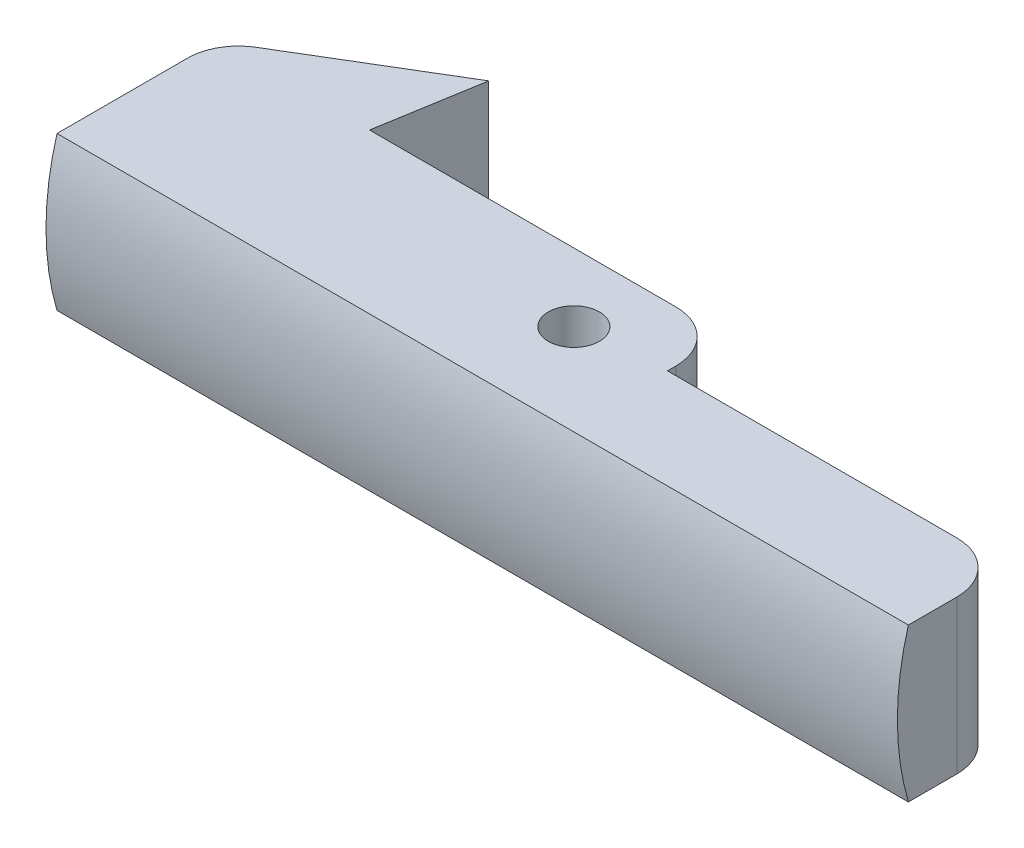
SolidWorks part; units mm, degrees
other "Marca1"
sketch "Croquis3" plane through (50, 10, -14) normal (0.2241, 0.9731, -0.0528) x (0.9657, -0.229, -0.1227)
ref_plane "Alzado" through (0, 0, 0) normal (0, 0, 1) x (1, 0, 0)
ref_plane "Planta" through (0, 0, 0) normal (0, 1, 0) x (1, 0, 0)
ref_plane "Vista lateral" through (0, 0, 0) normal (1, 0, 0) x (0, 0, -1)
sketch "Croquis1" plane through (0, 0, 0) normal (0, 1, 0) x (1, 0, 0)
  line L0 (0, 0) -> (0, 10)
  line L1 (0, 10) -> (10, 16)
  line L2 (10, 16) -> (9, 10)
  line L3 (9, 10) -> (50, 10)
  line L4 (50, 10) -> (50, 0)
  line L5 (50, 0) -> (0, 0)
  line L6 (0, 5) -> (50, 7) construction
  circle A0 centre (25, 6) radius 1.5
  dimension "D6" = 3
  dimension "D1" = 10
  dimension "D2" = 6
  dimension "D3" = 10
  dimension "D4" = 50
  dimension "D5" = 9
  dimension "D7" = 25
  dimension "D8" = 6
  dimension "D9" = 10
extrude "Saliente-Extruir1" add sketch "Croquis1" along normal blind 9
sketch "Croquis2" plane through (0, 9, 0) normal (0, 1, 0) x (1, 0, 0)
  line L0 (50, 10) -> (30, 10)
  line L1 (50, 10) -> (9, 10) construction
  line L2 (30, 10) -> (30, 6.5)
  line L3 (30, 6.5) -> (50, 6.5)
  line L4 (50, 0) -> (50, 10) construction
  line L5 (50, 6.5) -> (50, 10)
  dimension "D1" = 20
  dimension "D2" = 3.5
extrude "Cortar-Extruir1" cut sketch "Croquis2" against normal blind 18
fillet "Redondeo1" radius 3 3 edges at (0, 4.5, -10) (50, 4.5, -6.5) (30, 4.5, -10)
sketch "Croquis4" plane through (0, 0, 0) normal (-1, 0, 0) x (0, 0, 1)
  line L4 (0, 0) -> (0, 9)
  line L6 (0, 4.5) -> (-16, 4.5) construction
  line L7 (-16, 9) -> (-16, 0) construction
  line L8 (-0.6458, 9) -> (0, 9)
  line L9 (-8.3014, 9) -> (0, 9) construction
  line L10 (-0.6458, 0) -> (0, 0)
  arc A1 (-0.6458, 0) -> (-0.6458, 9) centre (-16, 4.5) ccw
  line M1 (0, 9) -> (-8.3014, 9)
  line M3 (-8.3014, 0) -> (0, 0)
  line M4 (0, 0) -> (0, 9)
extrude "Cortar-Extruir2" cut sketch "Croquis4" against normal blind 51 contours M4 M1 | M3 M4 region at (0, 1.1204, -0.1931) region at (0, 7.8796, -0.1931)
